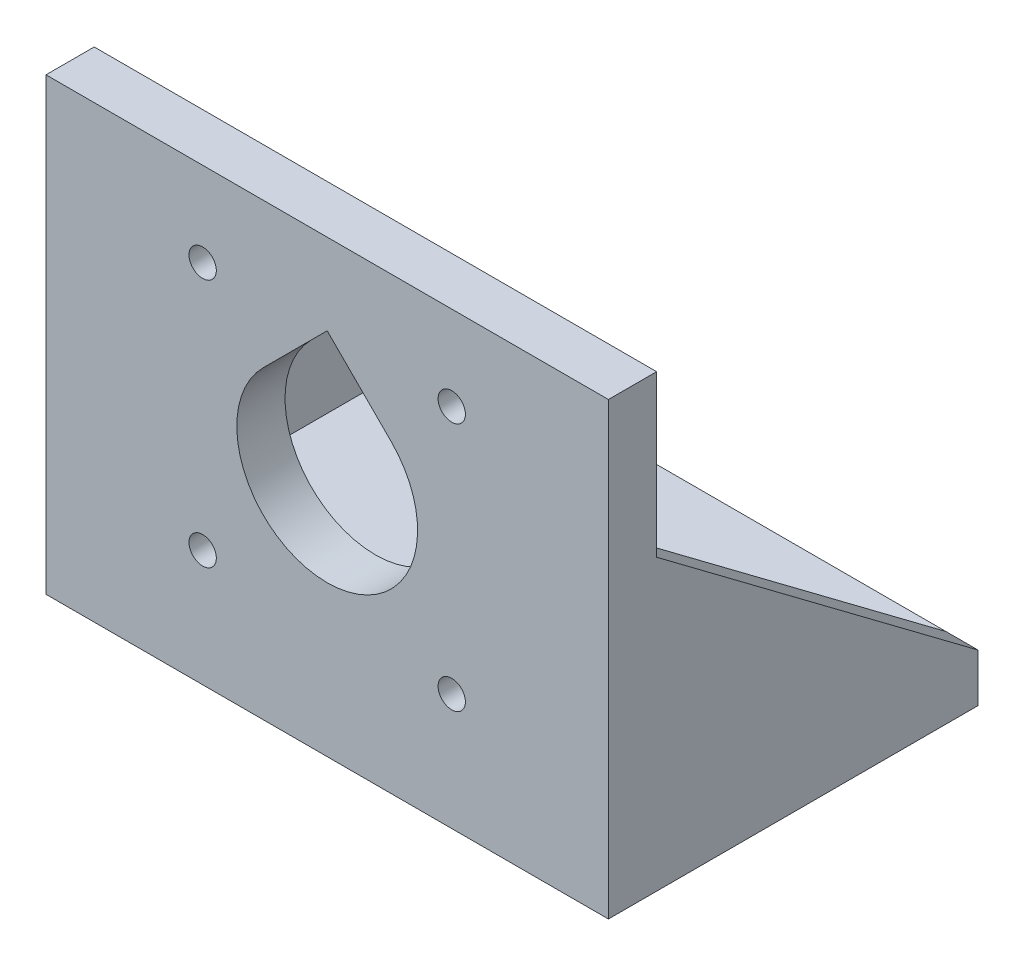
SolidWorks part; units mm, degrees
ref_plane "Спереди" through (0, 0, 0) normal (0, 0, 1) x (1, 0, 0)
ref_plane "Сверху" through (0, 0, 0) normal (0, 1, 0) x (1, 0, 0)
ref_plane "Справа" through (0, 0, 0) normal (1, 0, 0) x (0, 0, -1)
other "Configuration Table"
sketch "01_Пластина_эскиз" plane through (0, 0, 0) normal (0, 0, 1) x (1, 0, 0)
  line L1 (0, 0) -> (70, 0)
  line L2 (0, 0) -> (0, 56)
  line L3 (0, 56) -> (70, 56)
  line L4 (70, 0) -> (70, 56)
  dimension "D1" = 70
  dimension "D2" = 56
extrude "01_Передняя_пластина" add sketch "01_Пластина_эскиз" along normal blind 6
sketch "02_Полка_эскиз" plane through (0, 0, 0) normal (0, 1, 0) x (1, 0, 0)
  line L1 (0, 40) -> (70, 40)
  line L2 (0, 40) -> (0, -6)
  line L3 (0, -6) -> (70, -6)
  line L4 (70, 40) -> (70, -6)
  dimension "D1" = 70
  dimension "D2" = 46
  dimension "D3" = 6
  dimension "D4" = 6
extrude "02_Полка" add sketch "02_Полка_эскиз" along normal blind 6
sketch "03_Косынка_левая_эскиз" plane through (0, 0, 0) normal (1, 0, 0) x (0, 0, -1)
  line L0 (40, 6) -> (0, 6)
  line L1 (0, 6) -> (0, 36)
  line L2 (0, 36) -> (40, 6)
  dimension "D3" = 6
  dimension "D1" = 40
  dimension "D2" = 30
extrude "03_Косынка_левая" add sketch "03_Косынка_левая_эскиз" along normal blind 4
sketch "04_Косынка_правая_эскиз" plane through (0, 0, 0) normal (1, 0, 0) x (0, 0, -1)
  line L0 (40, 6) -> (0, 6)
  line L1 (0, 6) -> (0, 36)
  line L2 (0, 36) -> (40, 6)
  dimension "D3" = 6
  dimension "D1" = 40
  dimension "D2" = 30
extrude "04_Косынка_правая" add sketch "04_Косынка_правая_эскиз" along normal blind 4 from offset 66
sketch "05_Мотор_передний_фланец_эскиз" plane through (0, 0, 0) normal (0, 0, 1) x (1, 0, 0)
  circle A0 centre (35, 30) radius 11.25
  circle A1 centre (19.5, 14.5) radius 1.7
  circle A2 centre (19.5, 45.5) radius 1.7
  circle A3 centre (50.5, 14.5) radius 1.7
  circle A4 centre (50.5, 45.5) radius 1.7
  dimension "D1" = 3.4
  dimension "D2" = 3.4
  dimension "D3" = 3.4
  dimension "D4" = 3.4
  dimension "D5" = 22.5
  dimension "D6" = 15.5
  dimension "D7" = 31
  dimension "D8" = 15.5
  dimension "D9" = 31
  dimension "D10" = 35
  dimension "D11" = 30
extrude "05_Буртик_и_4_отверстия_М3" cut sketch "05_Мотор_передний_фланец_эскиз" against normal through all and the other way through all
sketch "06_Свод_45град_эскиз" plane through (0, 0, 0) normal (0, 0, 1) x (1, 0, 0)
  line L0 (27.045, 37.955) -> (42.955, 37.955)
  line L1 (42.955, 37.955) -> (35, 45.9099)
  line L2 (35, 45.9099) -> (27.045, 37.955)
  dimension "D1" = 7.955
  dimension "D2" = 15.9099
  dimension "D3" = 7.955
  dimension "D4" = 35
  dimension "D5" = 45.9099
extrude "06_Свод_отверстия_для_печати" cut sketch "06_Свод_45град_эскиз" against normal through all and the other way through all
sketch "07_Крепление_полки_эскиз" plane through (0, 0, 0) normal (0, 1, 0) x (1, 0, 0)
  circle A0 centre (8.5, 12) radius 2.25
  circle A1 centre (8.5, 30) radius 2.25
  circle A2 centre (61.5, 12) radius 2.25
  circle A3 centre (61.5, 30) radius 2.25
  dimension "D1" = 4.5
  dimension "D2" = 4.5
  dimension "D3" = 4.5
  dimension "D4" = 4.5
  dimension "D5" = 53
  dimension "D6" = 18
  dimension "D7" = 8.5
  dimension "D8" = 12
extrude "07_4_отверстия_М4" cut sketch "07_Крепление_полки_эскиз" against normal through all and the other way through all
equation "\"Ширина\"= 70"
equation "\"Высота пластины\"= 56"
equation "\"Толщина стенок\"= 6"
equation "\"Длина полки\"= 40"
equation "\"Толщина косынки\"= 4"
equation "\"Высота косынки\"= 30"
equation "\"Высота оси\"= 30"
equation "\"Шаг М3 ПРЕДВ\"= 31"
equation "\"Отверстие буртика\"= 22.5"
equation "\"Отверстия М3\"= 3.4"
equation "\"Отверстия М4\"= 4.5"
equation "\"Отступ М4 сбоку\"= 8.5"
equation "\"Ближний ряд М4\"= 12"
equation "\"Отступ М4 сзади\"= 10"
equation "\"D1@01_Пластина_эскиз\" = \"Ширина\""
equation "\"D2@01_Пластина_эскиз\" = \"Высота пластины\""
equation "\"D1@01_Передняя_пластина\" = \"Толщина стенок\""
equation "\"D1@02_Полка_эскиз\" = \"Ширина\""
equation "\"D2@02_Полка_эскиз\" = \"Длина полки\" + \"Толщина стенок\""
equation "\"D1@02_Полка\" = \"Толщина стенок\""
equation "\"D1@03_Косынка_левая_эскиз\" = \"Длина полки\""
equation "\"D2@03_Косынка_левая_эскиз\" = \"Высота косынки\""
equation "\"D1@03_Косынка_левая\" = \"Толщина косынки\""
equation "\"D1@04_Косынка_правая_эскиз\" = \"Длина полки\""
equation "\"D2@04_Косынка_правая_эскиз\" = \"Высота косынки\""
equation "\"D1@04_Косынка_правая\" = \"Толщина косынки\""
equation "\"D19@04_Косынка_правая\" = \"Ширина\" - \"Толщина косынки\""
equation "\"D1@05_Мотор_передний_фланец_эскиз\" = \"Отверстия М3\""
equation "\"D2@05_Мотор_передний_фланец_эскиз\" = \"Отверстия М3\""
equation "\"D3@05_Мотор_передний_фланец_эскиз\" = \"Отверстия М3\""
equation "\"D4@05_Мотор_передний_фланец_эскиз\" = \"Отверстия М3\""
equation "\"D5@05_Мотор_передний_фланец_эскиз\" = \"Отверстие буртика\""
equation "\"D6@05_Мотор_передний_фланец_эскиз\" = \"Шаг М3 ПРЕДВ\" / 2"
equation "\"D7@05_Мотор_передний_фланец_эскиз\" = \"Шаг М3 ПРЕДВ\""
equation "\"D8@05_Мотор_передний_фланец_эскиз\" = \"Шаг М3 ПРЕДВ\" / 2"
equation "\"D9@05_Мотор_передний_фланец_эскиз\" = \"Шаг М3 ПРЕДВ\""
equation "\"D1@07_Крепление_полки_эскиз\" = \"Отверстия М4\""
equation "\"D2@07_Крепление_полки_эскиз\" = \"Отверстия М4\""
equation "\"D3@07_Крепление_полки_эскиз\" = \"Отверстия М4\""
equation "\"D4@07_Крепление_полки_эскиз\" = \"Отверстия М4\""
equation "\"D5@07_Крепление_полки_эскиз\" = \"Ширина\" - 2 * \"Отступ М4 сбоку\""
equation "\"D3@02_Полка_эскиз\" = \"Толщина стенок\""
equation "\"D3@03_Косынка_левая_эскиз\" = \"Толщина стенок\""
equation "\"D3@04_Косынка_правая_эскиз\" = \"Толщина стенок\""
equation "\"D10@05_Мотор_передний_фланец_эскиз\" = \"Ширина\" / 2"
equation "\"D11@05_Мотор_передний_фланец_эскиз\" = \"Высота оси\""
equation "\"D1@06_Свод_45град_эскиз\" = \"Отверстие буртика\" / (2 * SQR(2))"
equation "\"D2@06_Свод_45град_эскиз\" = \"Отверстие буртика\" / SQR(2)"
equation "\"D3@06_Свод_45град_эскиз\" = \"Отверстие буртика\" / (2 * SQR(2))"
equation "\"D4@06_Свод_45град_эскиз\" = \"Ширина\" / 2"
equation "\"D5@06_Свод_45град_эскиз\" = \"Высота оси\" + \"Отверстие буртика\" / SQR(2)"
equation "\"D6@07_Крепление_полки_эскиз\" = \"Длина полки\" - \"Ближний ряд М4\" - \"Отступ М4 сзади\""
equation "\"D7@07_Крепление_полки_эскиз\" = \"Отступ М4 сбоку\""
equation "\"D8@07_Крепление_полки_эскиз\" = \"Ближний ряд М4\""
